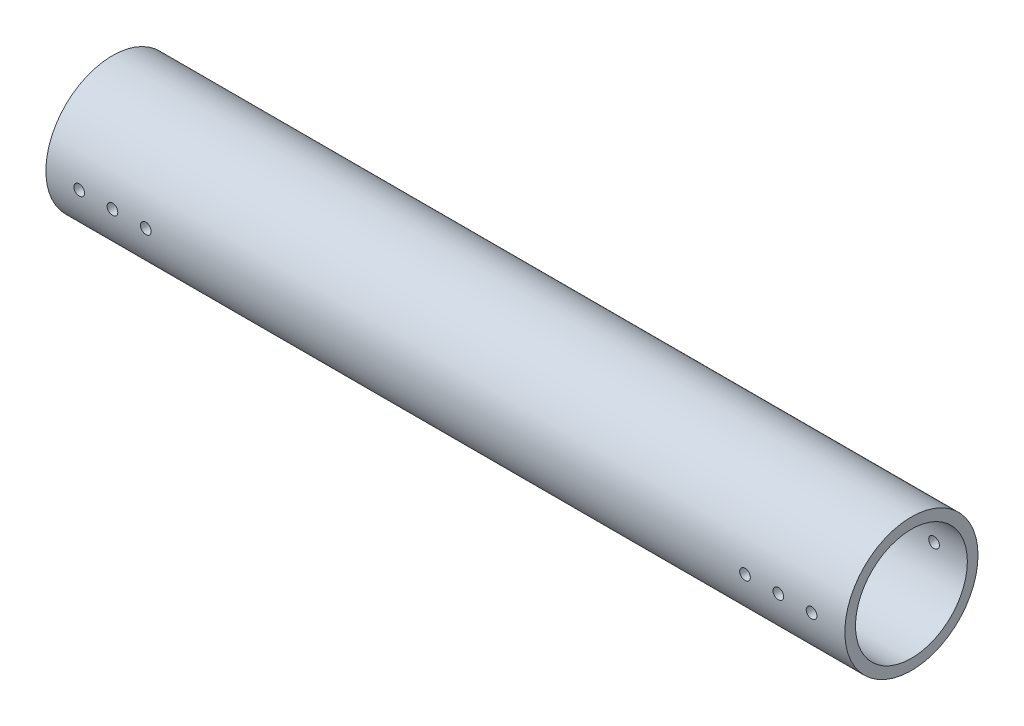
SolidWorks part; units mm, degrees
material "Zoltek Panex 33"
ref_plane "Спереди" through (0, 0, 0) normal (0, 0, 1) x (1, 0, 0)
ref_plane "Сверху" through (0, 0, 0) normal (0, 1, 0) x (1, 0, 0)
ref_plane "Справа" through (0, 0, 0) normal (1, 0, 0) x (0, 0, -1)
other "Configuration Table"
sketch "Эскиз2" plane through (0, 0, 0) normal (1, 0, 0) x (0, 0, -1)
  circle A0 centre (0, 0) radius 25
  circle A1 centre (0, 0) radius 21
  dimension "D1" = 50
  dimension "D2" = 42
extrude "Бобышка-Вытянуть2" add sketch "Эскиз2" along normal blind 300
ref_plane "Плоскость1" through (0, 0, 25) normal (0, 0, 1) x (1, 0, 0)
sketch "Эскиз4" plane through (0, 0, 25) normal (0, 0, 1) x (1, 0, 0)
  line L0 (0, -25) -> (300, -25) construction
  line L1 (300, -25) -> (300, 25) construction
  circle A0 centre (12.5, 0) radius 2
  circle A1 centre (287.5, 0) radius 2
  circle A2 centre (25, 0) radius 2
  circle A3 centre (37.5, 0) radius 2
  circle A4 centre (275, 0) radius 2
  circle A5 centre (262.5, 0) radius 2
  dimension "D1" = 4
  dimension "D4" = 4
  dimension "D6" = 4
  dimension "D8" = 4
  dimension "D10" = 4
  dimension "D11" = 4
  dimension "D2" = 12.5
  dimension "D3" = 25
  dimension "D5" = 12.5
  dimension "D7" = 12.5
  dimension "D9" = 12.5
  dimension "15" = 12.5
  dimension "D12" = 12.5
extrude "Вырез-Вытянуть2" cut sketch "Эскиз4" against normal through all and the other way blind 10 contours A0 | A1 | A2 | A3 | A5 | A4
equation "\"Diameter\"= 50мм"
equation "\"D1@Эскиз2\"= \"Diameter\""
equation "\"Length\"= 300мм"
equation "\"Thickness\"= 4мм"
equation "\"D1@Бобышка-Вытянуть2\"= \"Length\""
equation "\"D2@Эскиз2\" = \"Diameter\" - \"Thickness\" * 2"
equation "\"D4@Эскиз4\"=\"D1@Эскиз4\""
equation "\"D5@Эскиз4\"=\"D2@Эскиз4\""
equation "\"D3@Эскиз4\"=\"Diameter\"/2"
equation "\"D6@Эскиз4\"=\"D1@Эскиз4\""
equation "\"D8@Эскиз4\"=\"D6@Эскиз4\""
equation "\"D10@Эскиз4\"=\"D4@Эскиз4\""
equation "\"D11@Эскиз4\"=\"D4@Эскиз4\""
equation "\"D9@Эскиз4\"=\"D7@Эскиз4\""
